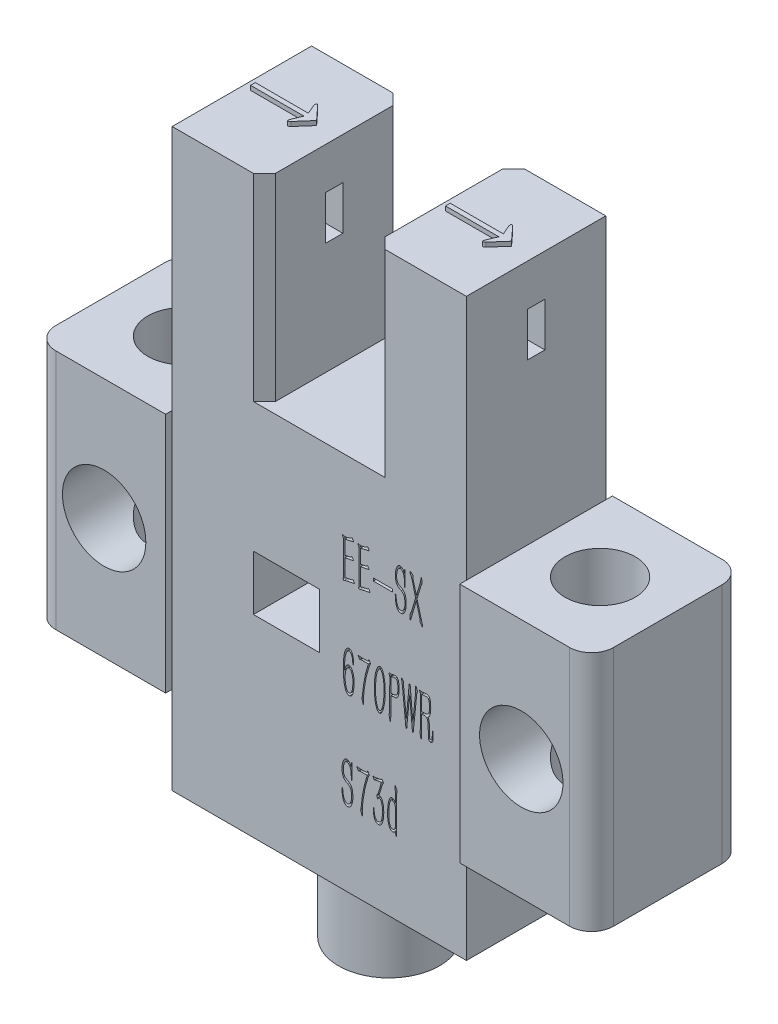
SolidWorks part; units mm, degrees
ref_plane "前视基准面" through (0, 0, 0) normal (0, 0, 1) x (1, 0, 0)
ref_plane "上视基准面" through (0, 0, 0) normal (0, 1, 0) x (1, 0, 0)
ref_plane "右视基准面" through (0, 0, 0) normal (1, 0, 0) x (0, 0, -1)
sketch "草图1" plane through (0, 0, 0) normal (0, 0, 1) x (1, 0, 0)
  line L0 (0, -23.5178) -> (0, 26.8466) construction
  line L1 (-12.7, -5.5) -> (-6.7, -5.5)
  line L2 (-12.7, -5.5) -> (-12.7, 5.5)
  line L3 (-12.7, 5.5) -> (-6.7, 5.5)
  line L4 (12.7, -5.5) -> (12.7, 5.5)
  line L5 (-12.7, -5.5) -> (12.7, 5.5) construction
  line L6 (-12.7, 5.5) -> (12.7, -5.5) construction
  line L7 (-6.7, -9.5) -> (6.7, -9.5)
  line L8 (-6.7, -9.5) -> (-6.7, -5.5)
  line L9 (-6.7, 16.7) -> (-2.5, 16.7)
  line L10 (6.7, -9.5) -> (6.7, -5.5)
  line L11 (2.5, 7.7) -> (-2.5, 7.7)
  line L12 (2.5, 7.7) -> (2.5, 16.7)
  line L13 (2.5, 16.7) -> (-2.5, 16.7) construction
  line L14 (-2.5, 7.7) -> (-2.5, 16.7)
  line L15 (2.5, 7.7) -> (-2.5, 16.7) construction
  line L16 (2.5, 16.7) -> (-2.5, 7.7) construction
  line L17 (0, -0.7) -> (-3, -0.7)
  line L18 (0, -0.7) -> (0, 1.8)
  line L19 (0, 1.8) -> (-3, 1.8)
  line L20 (-3, -0.7) -> (-3, 1.8)
  line L21 (6.7, 5.5) -> (12.7, 5.5)
  line L23 (-6.7, 5.5) -> (-6.7, 16.7)
  line L24 (6.7, 5.5) -> (6.7, 16.7)
  line L25 (6.7, -5.5) -> (6.7, 5.5)
  line L26 (6.7, -5.5) -> (12.7, -5.5)
  line L27 (2.5, 16.7) -> (6.7, 16.7)
  line L28 (-2.5, 16.7) -> (2.5, 16.7) construction
  line L29 (-6.7, 5.5) -> (-6.7, -5.5)
  circle A0 centre (9.5, 0) radius 1.9
  circle A1 centre (-9.5, 0) radius 1.9
  point P0 (0, 0)
  point P6 (0, 0)
  point P11 (0, 12.2)
  point P27 (0, 0)
  point P30 (0, 0)
  dimension "D9" = 3.8
  dimension "D1" = 25.4
  dimension "D2" = 26.2
  dimension "D3" = 11
  dimension "D4" = 11.2
  dimension "D5" = 9
  dimension "D6" = 3
  dimension "D7" = 13.4
  dimension "D8" = 5
  dimension "D10" = 2.5
  dimension "D11" = 8.4
  dimension "D12" = 19
  dimension "D13" = 5.5
extrude "凸台-拉伸1" add sketch "草图1" along normal mid plane 6.35 contours L23 L29 L8 L7 L10 L25 L24 L27 L12 L11 L14 L9 L17 L20 L19 L18 region at (0.0377, 2.3805, 0)
extrude "凸台-拉伸2" add sketch "草图1<3>" along normal mid plane 6.95 contours L29 L3 L2 L1 A1 | L25 L26 L4 L21 A0 region at (-12.5747, 0, 0) region at (6.8253, 0, 0)
sketch "草图1<3>" plane through (0, 0, 0) normal (0, 0, 1) x (1, 0, 0) same geometry as "草图1"
fillet "圆角1" radius 1 4 edges at (12.7, 0, 3.475) (12.7, 0, -3.475) (-12.7, 0, 3.475) (-12.7, 0, -3.475)
chamfer "倒角1" distance 0.5 angle 45 4 edges at (2.5, 12.2, -3.175) (2.5, 12.2, 3.175) (-2.5, 12.2, -3.175) (-2.5, 12.2, 3.175)
sketch "草图2" plane through (0, 0, 0) normal (1, 0, 0) x (0, 0, -1)
  line L1 (-0.4, 14.8) -> (0.4, 14.8)
  line L2 (-0.4, 14.8) -> (-0.4, 12.8)
  line L3 (-0.4, 12.8) -> (0.4, 12.8)
  line L4 (0.4, 14.8) -> (0.4, 12.8)
  line L6 (0, 5.5) -> (0, 16.7) construction
  line L7 (-2.475, 5.5) -> (2.475, 5.5) construction
  line L8 (-3.175, 16.7) -> (3.175, 16.7) construction
  line L10 (-2.675, 16.7) -> (2.675, 16.7) construction
  point P4 (-0.4, 13.8)
  dimension "D1" = 0.8
  dimension "D2" = 2
  dimension "D3" = 2.9
extrude "切除-拉伸1" cut sketch "草图2" against normal through all both and the other way through all
sketch "草图3" plane through (0, 16.7, 0) normal (0, 1, 0) x (1, 0, 0)
  line L0 (-6.7, -3.175) -> (-6.7, 3.175) construction
  line L1 (-6.7, -3.175) -> (-6.7, 3.175) construction
  text T0 "→"
  text T1 "→"
extrude "凸台-拉伸3" add sketch "草图3" along normal blind 0.2
sketch "草图4" plane through (0, -9.5, 0) normal (0, -1, 0) x (1, 0, 0)
  circle A0 centre (0, 0) radius 2.3
  dimension "D1" = 4.6
extrude "凸台-拉伸4" add sketch "草图4" along normal blind 4
sketch "草图5" plane through (0, 5.5, 0) normal (0, 1, 0) x (1, 0, 0)
  circle A0 centre (-9.3846, 0) radius 1.6
  circle A1 centre (9.6154, 0) radius 1.6
  point P4 (0, 0)
  dimension "D1" = 19
  dimension "D2" = 3.2
extrude "切除-拉伸3" cut sketch "草图5" against normal blind 19
sketch "草图6" plane through (0, 0, 3.175) normal (0, 0, 1) x (1, 0, 0)
  text T0 "EE-SX\r\n670PWR\r\nS73d" font "汉仪长仿宋体" height 2
extrude "切除-拉伸4" cut sketch "草图6" against normal blind 2
equation "\"D3@草图2\"=11.2+11-13.8-5.5"
